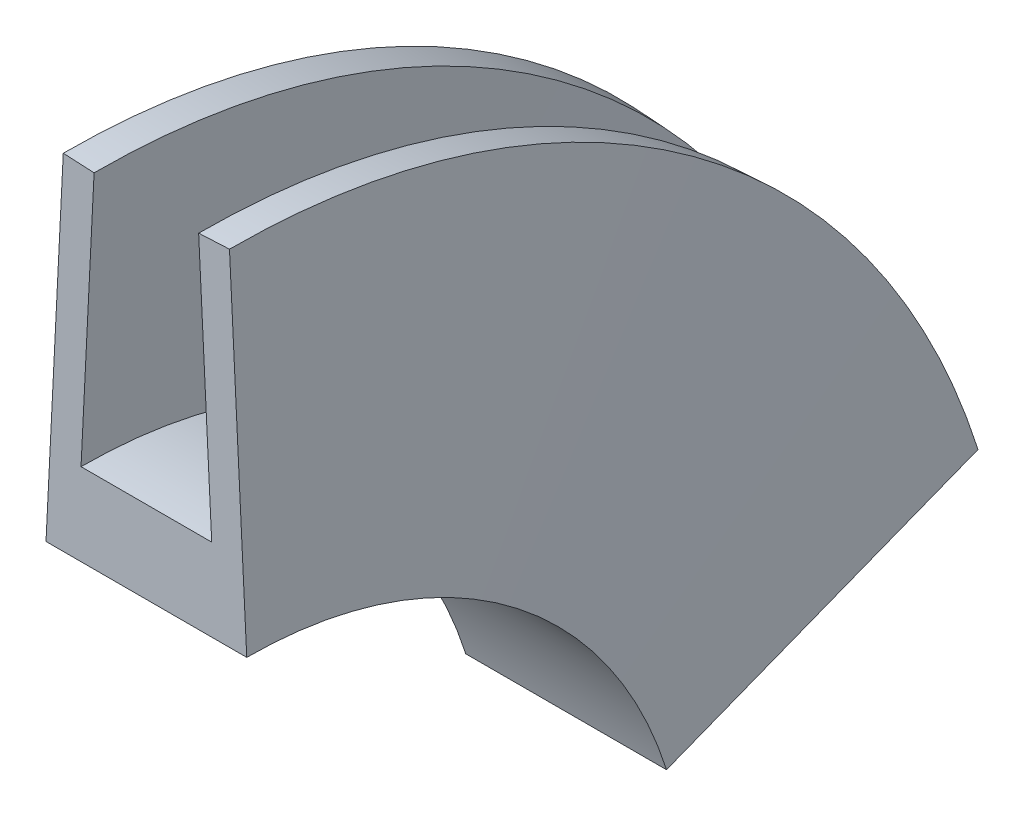
SolidWorks part; units mm, degrees
ref_plane "Front Plane" through (0, 0, 0) normal (0, 0, 1) x (1, 0, 0)
ref_plane "Top Plane" through (0, 0, 0) normal (0, 1, 0) x (1, 0, 0)
ref_plane "Right Plane" through (0, 0, 0) normal (1, 0, 0) x (0, 0, -1)
sketch "Sketch1" plane through (0, 0, 0) normal (0, 0, 1) x (1, 0, 0)
  line L1 (-2.0191, 6.3796) -> (-2.4386, -2)
  line L2 (-2.4386, -2) -> (2.4386, -2)
  line L3 (2.4386, -2) -> (2.0191, 6.3796)
  line L4 (2.0191, 6.3796) -> (1.27, 6.3421)
  line L5 (1.27, 6.3421) -> (1.5875, 0)
  line L6 (1.5875, 0) -> (-1.5875, 0)
  line L8 (-1.5875, 0) -> (-1.27, 6.3421)
  line L9 (-1.27, 6.3421) -> (-2.0191, 6.3796)
  point P0 (0, 0)
  dimension "D1" = 3.175
  dimension "D2" = 2
  dimension "D3" = 0.75
  dimension "D4" = 2.54
  dimension "D5" = 6.35
sketch "Sketch2" plane through (0, 0, 0) normal (1, 0, 0) x (0, 0, -1)
  circle A0 centre (0, -12.7) radius 12.7
  point P3 (12.105, -8.8583)
  point P5 (0, 0)
  dimension "D1" = 25.4
  dimension "D2" = 15
sketch "Sketch3" plane through (0, 0, 0) normal (1, 0, 0) x (0, 0, -1)
  circle A0 centre (0, -12.7) radius 12.7 construction
  arc A1 (0, 0) -> (12.105, -8.8583) centre (0, -12.7) cw
sweep "Sweep1" add profiles "Sketch1" path "Sketch3"
